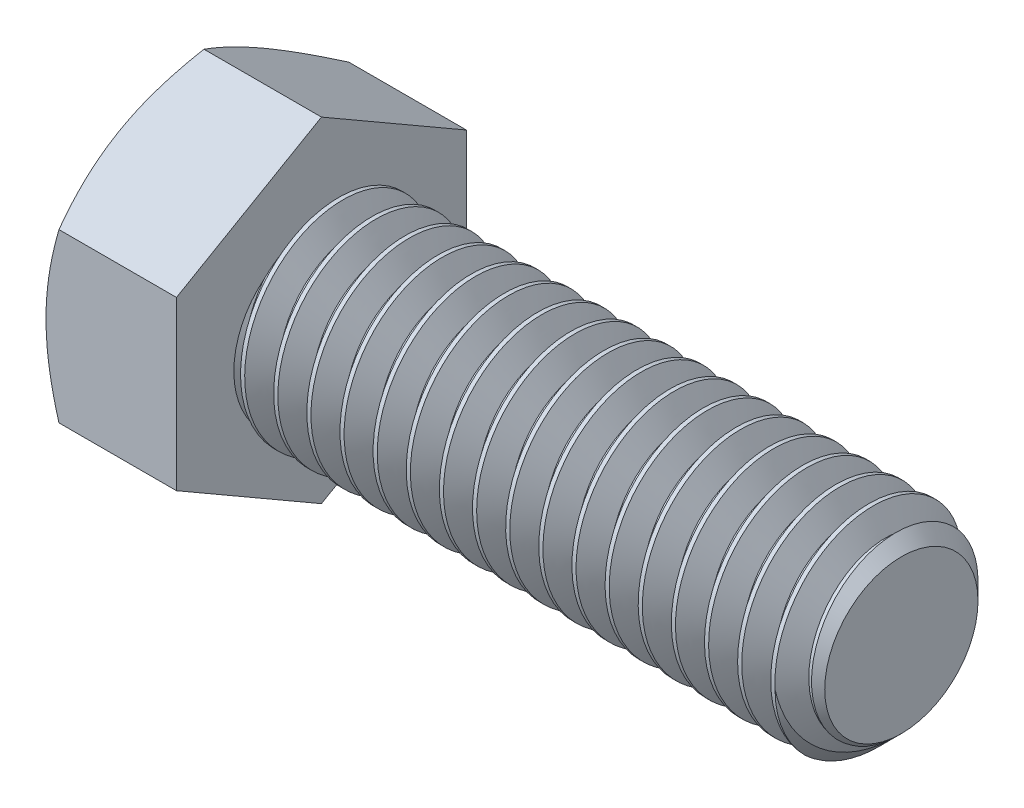
SolidWorks part; units mm, degrees
ref_plane "Front Plane" through (0, 0, 0) normal (0, 0, 1) x (1, 0, 0)
ref_plane "Top Plane" through (0, 0, 0) normal (0, 1, 0) x (1, 0, 0)
ref_plane "Right Plane" through (0, 0, 0) normal (1, 0, 0) x (0, 0, -1)
sketch "Sketch1" plane through (0, 0, 0) normal (0, 0, 1) x (1, 0, 0)
  line L0 (-19.4469, 0) -> (19.4469, 0) construction
  line L1 (19.4469, 5.5562) -> (19.4469, -5.5562) construction
  line L2 (-12.3031, 7.9375) -> (-12.3031, -7.9375) construction
  line L3 (-19.4469, 7.9375) -> (-19.4469, -7.9375) construction
  point P9 (-12.3031, 0)
  point P10 (13.0969, -5.5562)
  dimension "Screw Dia" = 11.1125
  dimension "Hex" = 15.875
  dimension "Head Ht" = 7.1437
  dimension "Screw Lenght" = 31.75
  dimension "D1" = 6.35
ref_plane "Plane2" through (19.4469, 0, 0) normal (1, 0, 0) x (0, 0, -1)
sketch "Sketch5" plane through (19.4469, 0, 0) normal (1, 0, 0) x (0, 0, -1)
  circle A0 centre (0, 0) radius 5.5562
extrude "Boss-Extrude3" add sketch "Sketch5" against normal up to vertex (31.75 mm away) up to point (-12.3031, 0, 0)
sketch "Sketch9" plane through (19.4469, 0, 0) normal (1, 0, 0) x (0, 0, -1)
  circle A1 centre (0, 0) radius 5.5562
  circle A2 centre (0, 0) radius 5.5562
  dimension "D1" = 0
curve "Helix/Spiral1" pitch 1.8143 height 33.5643 turns 18.5 parameters "Pitch"=1.8143
chamfer "Chamfer1" distance 1.3607 angle 45 1 edges at (19.4469, 0, -5.5562)
sketch "Sketch10" plane through (0, 0, 0) normal (0, 0, 1) x (1, 0, 0)
  line L0 (19.4469, 5.5562) -> (20.1272, 4.3778)
  line L1 (20.1272, 4.3778) -> (20.354, 4.3778)
  line L2 (20.354, 4.3778) -> (21.0344, 5.5563)
  line L3 (19.4469, 5.5562) -> (21.0344, 5.5563)
  line L4 (20.2406, 5.5562) -> (20.2406, 4.3778) construction
  line L5 (19.7871, 4.967) -> (20.6942, 4.967) construction
  dimension "D1" = 60
  dimension "D2" = 0.2268
  dimension "D3" = 0.9071
sweep "Cut-Sweep1" cut profiles "Sketch10" path "Helix/Spiral1"
sketch "Sketch6" plane through (-12.3031, 0, 0) normal (-1, 0, 0) x (0, 0, 1)
  line L0 (0, 7.9375) -> (0, -7.9375) construction
  line L1 (7.9375, 4.5827) -> (0, 9.1654)
  line L2 (0, 9.1654) -> (-7.9375, 4.5827)
  line L3 (-7.9375, 4.5827) -> (-7.9375, -4.5827)
  line L4 (-7.9375, -4.5827) -> (0, -9.1654)
  line L5 (0, -9.1654) -> (7.9375, -4.5827)
  line L6 (7.9375, -4.5827) -> (7.9375, 4.5827)
  circle A0 centre (0, 0) radius 7.9375 construction
extrude "Boss-Extrude4" add sketch "Sketch6" along normal up to vertex (7.1437 mm away) up to point (-19.4469, -7.9375, 0)
sketch "Sketch7" plane through (-19.4469, 0, 0) normal (-1, 0, 0) x (0, 0, 1)
  circle A0 centre (0, 0) radius 7.9375 construction
  circle A1 centre (0, 0) radius 7.9375
sketch "Sketch8" plane through (-19.4469, 0, 0) normal (-1, 0, 0) x (0, 0, 1)
  circle A0 centre (0, 0) radius 7.9375 construction
  circle A1 centre (0, 0) radius 7.9375
extrude "Cut-Extrude3" cut sketch "Sketch8" against normal through all draft 60 flip side to cut
equation "\"D2@Sketch10\" = \"Pitch@Helix/Spiral1\"*.125"
equation "\"D3@Sketch10\" = \"Pitch@Helix/Spiral1\"*.5"
equation "\"D3@Helix/Spiral1\" = \"Screw Lenght@Sketch1\"+\"Pitch@Helix/Spiral1\""
equation "\"D1@Chamfer1\" = \"Pitch@Helix/Spiral1\"*.75"
equation "\"D1@Sketch1\" = \"Pitch@Helix/Spiral1\"*3.5"
